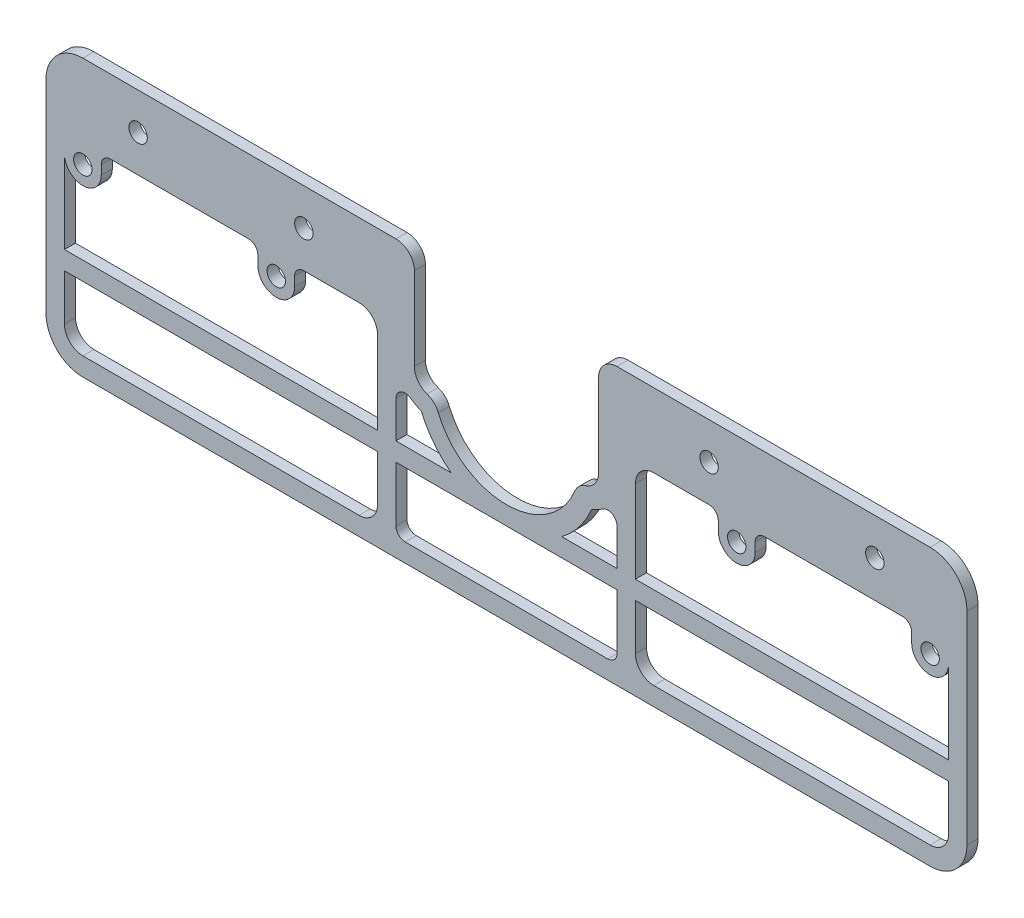
SolidWorks part; units mm, degrees
ref_plane "Front Plane" through (0, 0, 0) normal (0, 0, 1) x (1, 0, 0)
ref_plane "Top Plane" through (0, 0, 0) normal (0, 1, 0) x (1, 0, 0)
ref_plane "Right Plane" through (0, 0, 0) normal (1, 0, 0) x (0, 0, -1)
sketch "Sketch1" plane through (0, 0, 0) normal (0, 0, 1) x (1, 0, 0)
  line L0 (-40, 20) -> (-40, 55) construction
  line L4 (-250, -55) -> (-250, 3.1783)
  line L8 (-50, 75) -> (-230, 75) construction
  line L17 (0, -20) -> (0, -40)
  line L25 (0, -65) -> (0, -75)
  line L26 (0, 75) -> (0, -75) construction
  line L27 (-50, 95) -> (50, 95) construction
  line L34 (0, -75) -> (-230, -75)
  line L156 (-50, 75) -> (-230, 75) construction
  line L161 (0, -40) -> (0, -65)
  line L165 (-164.3309, 75) -> (-60, 75)
  line L167 (-230, 75) -> (-220, 75)
  line L171 (-250, 3.1783) -> (-250, 55)
  line L172 (-220, 75) -> (-164.3309, 75)
  line L173 (-50, 65) -> (-50, 20)
  arc A0 (-40, 20) -> (0, -20) centre (0, 20) ccw construction
  circle A1 centre (0, 20) radius 30 construction
  arc A4 (-230, -75) -> (-250, -55) centre (-230, -55) cw
  arc A5 (-250, 55) -> (-230, 75) centre (-230, 55) cw
  arc A124 (0, -20) -> (-37, 4.8013) centre (0, 20) cw
  arc A125 (-60, 75) -> (-50, 65) centre (-60, 65) cw
  arc A126 (-43.125, 10.5008) -> (-50, 20) centre (-40, 20) cw
  arc A127 (-37, 4.8013) -> (-43.125, 10.5008) centre (-46.25, 1.0016) ccw
  point P0 (0, 0)
  point P10 (-50, 10)
  point P11 (0, 50)
  point P30 (-40, 75)
  point P45 (0, -30)
  point P74 (0, 95)
  dimension "D3" = 80
  dimension "D4" = 60
  dimension "D6" = 55
  dimension "D7" = 75
  dimension "D10" = 10
  dimension "D11" = 20
  dimension "D8" = 10
  dimension "D5" = 10
  dimension "D9" = 20
  dimension "D13" = 210
  dimension "D16" = 100
  dimension "D17" = 20
  dimension "D26" = 250
extrude "Boss-Extrude1" add sketch "Sketch1" along normal blind 6
mirror "Mirror1" about plane through (0, -20, 6) normal (-1, 0, 0) of "Boss-Extrude1"
sketch "Sketch3" plane through (0, 0, 6) normal (0, 0, 1) x (1, 0, 0)
  line L3 (50, 20) -> (50, 65) construction
  line L4 (50, 20) -> (50, 65) construction
  line L7 (-60, 75) -> (-230, 75) construction
  line L8 (-250, 55) -> (-250, -55) construction
  line L9 (250, 55) -> (250, -55) construction
  circle A2 centre (110, 55) radius 5
  circle A3 centre (200, 55) radius 5
  circle A4 centre (-200, 55) radius 5
  circle A5 centre (-110, 55) radius 5
  dimension "D3" = 10
  dimension "D4" = 10
  dimension "D5" = 10
  dimension "D6" = 10
  dimension "D8" = 20
  dimension "D12" = 50
  dimension "D2" = 140
  dimension "D7" = 20
  dimension "D9" = 50
  dimension "D10" = 140
extrude "Cut-Extrude1" cut sketch "Sketch3" against normal through all contours A2 | A3 | A5 | A4 region at (110, 55, 6) region at (200, 55, 6) region at (-110, 55, 6)
sketch "Sketch4" plane through (0, 0, 6) normal (0, 0, 1) x (1, 0, 0)
  line L0 (-230, -75) -> (230, -75) construction
  line L1 (-70, 25) -> (-70, -55)
  line L2 (-50, 20) -> (-50, 65) construction
  line L3 (-60, 75) -> (-230, 75) construction
  line L7 (-240, -55) -> (-240, 25)
  line L8 (-250, 55) -> (-250, -55) construction
  line L9 (-210, -65) -> (-190, -65)
  line L10 (-115, 25) -> (-115, 30)
  line L11 (-110, 35) -> (-80, 35)
  line L12 (-220, 25) -> (-220, 30)
  line L13 (-215, 35) -> (-140, 35)
  line L14 (-135, 30) -> (-135, 25)
  line L15 (-230, -65) -> (-210, -65)
  line L16 (-110, -65) -> (-90, -65)
  line L17 (0, 0) -> (0, -75) construction
  line L18 (-190, -65) -> (-110, -65)
  line L19 (90, -65) -> (80, -65)
  line L20 (190, -65) -> (110, -65)
  line L21 (-90, -65) -> (-80, -65)
  line L22 (110, -65) -> (90, -65)
  line L23 (230, -65) -> (210, -65)
  line L24 (230, 25) -> (125, 25) construction
  line L30 (221.3397, 20) -> (133.6603, 20)
  line L32 (110, 35) -> (80, 35)
  line L33 (115, 25) -> (115, 30)
  line L35 (210, -65) -> (190, -65)
  line L36 (240, -55) -> (240, 25)
  line L37 (70, 25) -> (70, -55)
  line L38 (125, 35) -> (230, 35)
  line L39 (230, 20) -> (125, 20) construction
  circle A0 centre (-230, 25) radius 5
  circle A3 centre (-125, 25) radius 5
  arc A6 (-230, -65) -> (-240, -55) centre (-230, -55) cw
  arc A8 (-222.2775, 18.6468) -> (-231.6408, 15.1355) centre (-230, 25) ccw
  arc A9 (-127.2754, 15.2623) -> (-127.1893, 15.2426) centre (-125, 25) ccw
  arc A12 (-110, 35) -> (-115, 30) centre (-110, 30) ccw
  arc A13 (-140, 35) -> (-135, 30) centre (-140, 30) cw
  arc A14 (-215, 35) -> (-220, 30) centre (-215, 30) ccw
  arc A15 (-70, -55) -> (-80, -65) centre (-80, -55) cw
  arc A16 (-70, 25) -> (-80, 35) centre (-80, 25) ccw
  arc A17 (-117.6445, 18.2253) -> (-134.5708, 22.1017) centre (-125, 25) ccw
  arc A19 (-231.6408, 15.1355) -> (-222.2775, 18.6468) centre (-230, 25) ccw
  arc A20 (-134.5708, 22.1017) -> (-117.3815, 18.5225) centre (-125, 25) ccw
  arc A21 (133.6603, 20) -> (117.3815, 18.5225) centre (125, 25) cw
  arc A22 (231.6408, 15.1355) -> (222.2775, 18.6468) centre (230, 25) cw
  arc A23 (117.6445, 18.2253) -> (125, 35) centre (125, 25) cw
  arc A24 (70, 25) -> (80, 35) centre (80, 25) cw
  arc A25 (70, -55) -> (80, -65) centre (80, -55) ccw
  arc A26 (230, 35) -> (231.6408, 15.1355) centre (230, 25) cw
  arc A28 (110, 35) -> (115, 30) centre (110, 30) cw
  arc A29 (127.2754, 15.2623) -> (127.1893, 15.2426) centre (125, 25) cw
  arc A30 (222.2775, 18.6468) -> (221.3397, 20) centre (230, 25) cw
  arc A31 (230, -65) -> (240, -55) centre (230, -55) ccw
  circle A32 centre (125, 25) radius 5
  circle A33 centre (230, 25) radius 5
  point P0 (0, -75)
  dimension "D1" = 10
  dimension "D13" = 10
  dimension "D14" = 20
  dimension "D10" = 5
  dimension "D15" = 5
  dimension "D17" = 10
  dimension "D2" = 230
  dimension "D4" = 5
  dimension "D5" = 125
  dimension "D8" = 50
  dimension "D9" = 10
  dimension "D11" = 20
  dimension "D12" = 80
  dimension "D16" = 80
extrude "Cut-Extrude2" cut sketch "Sketch4" against normal through all contours A20 A17 L14 A13 L13 A14 L12 A8 A19 L7 A6 L15 L9 L18 L16 L21 A15 L1 A16 L11 A12 L10 A9 | A0 | A3 region at (-154.1168, -16.7892, 6) region at (-230, 25, 6) region at (-125, 25, 6)
sketch "Sketch8" plane through (0, 0, 6) normal (0, 0, 1) x (1, 0, 0)
  line L0 (-60, 0) -> (-60, -65)
  line L2 (-60, -65) -> (60, -65)
  line L3 (60, -65) -> (60, 0)
  line L4 (-230, -65) -> (-80, -65) construction
  arc A0 (43.125, 10.5008) -> (50, 20) centre (40, 20) ccw construction
  arc A1 (43.125, 10.5008) -> (37, 4.8013) centre (46.25, 1.0016) ccw construction
  arc A2 (-37, 4.8013) -> (-43.125, 10.5008) centre (-46.25, 1.0016) ccw construction
  arc A3 (-50, 20) -> (-43.125, 10.5008) centre (-40, 20) ccw construction
  arc A4 (-37, 4.8013) -> (37, 4.8013) centre (0, 20) ccw construction
  arc A5 (43.125, 10.5008) -> (50, 20) centre (40, 20) ccw construction
  arc A6 (43.125, 10.5008) -> (37, 4.8013) centre (46.25, 1.0016) ccw construction
  arc A7 (-37, 4.8013) -> (-43.125, 10.5008) centre (-46.25, 1.0016) ccw construction
  arc A8 (-50, 20) -> (-43.125, 10.5008) centre (-40, 20) ccw construction
  arc A9 (-37, 4.8013) -> (37, 4.8013) centre (0, 20) ccw construction
  arc A10 (-52, 4) -> (-46.25, 1.0016) centre (-40, 20) ccw
  arc A11 (-46.25, 1.0016) -> (-46.25, 1.0016) centre (-46.25, 1.0016) ccw
  arc A12 (-46.25, 1.0016) -> (46.25, 1.0016) centre (0, 20) ccw
  arc A13 (46.25, 1.0016) -> (46.25, 1.0016) centre (46.25, 1.0016) ccw
  arc A14 (46.25, 1.0016) -> (52, 4) centre (40, 20) ccw
  arc A15 (46.25, 1.0016) -> (60, 20) centre (40, 20) ccw construction
  arc A16 (60, 0) -> (52, 4) centre (55, 0) ccw
  arc A17 (-60, 20) -> (-46.25, 1.0016) centre (-40, 20) ccw construction
  arc A18 (-60, 0) -> (-52, 4) centre (-55, 0) cw
  dimension "D2" = 5
  dimension "D1" = 10
extrude "Cut-Extrude5" cut sketch "Sketch8" against normal through all
fillet "Fillet5" radius 5 1 edges at (-60, -65, 3)
fillet "Fillet6" radius 5 1 edges at (60, -65, 3)
mirror "Mirror2" about plane through (0, 0, 0) normal (1, 0, 0) of "Cut-Extrude2"
sketch "Sketch9" plane through (0, 0, 6) normal (0, 0, 1) x (1, 0, 0)
  line L0 (-250, -20) -> (250, -20)
  line L1 (-250, 55) -> (-250, -55) construction
  line L2 (250, 55) -> (250, -55) construction
  line L3 (250, -20) -> (250, -30)
  line L4 (250, -30) -> (-250, -30)
  line L5 (-250, -30) -> (-250, -20)
  arc A0 (-37, 4.8013) -> (37, 4.8013) centre (0, 20) ccw construction
  arc A1 (-46.25, 1.0016) -> (46.25, 1.0016) centre (0, 20) ccw construction
extrude "Boss-Extrude2" add sketch "Sketch9" against normal up to surface (6 mm away) up to face at (225, 25, 0)
